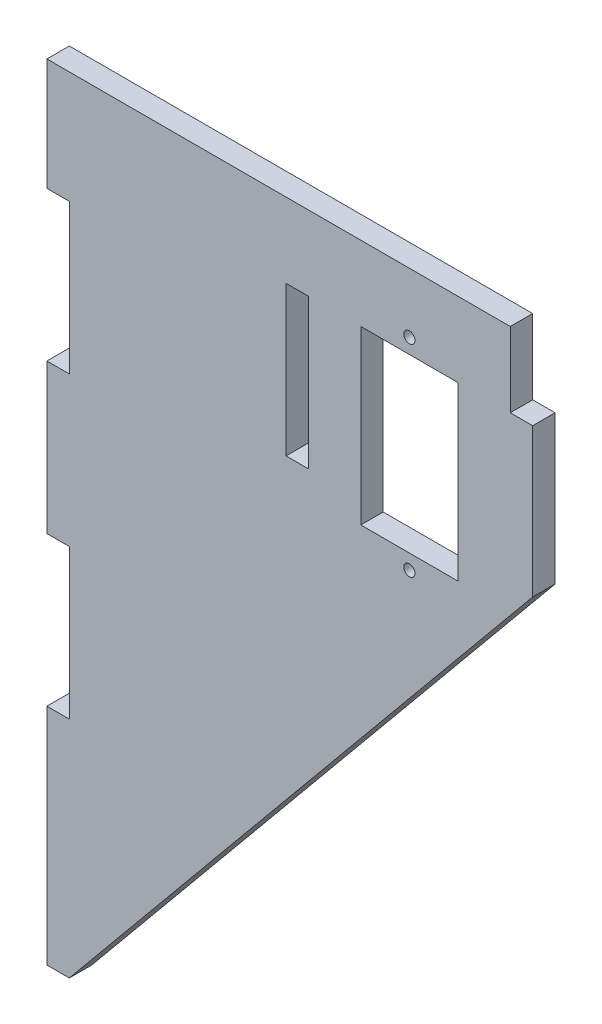
SolidWorks part; units mm, degrees
material "Acrilico TEC"
ref_plane "Front Plane" through (0, 0, 0) normal (0, 0, 1) x (1, 0, 0)
ref_plane "Top Plane" through (0, 0, 0) normal (0, 1, 0) x (1, 0, 0)
ref_plane "Right Plane" through (0, 0, 0) normal (1, 0, 0) x (0, 0, -1)
sketch "Sketch1" plane through (0, 0, 0) normal (0, 0, 1) x (1, 0, 0)
  line L0 (-3, 70) -> (-3, 50)
  line L1 (-3, 50) -> (0, 50)
  line L2 (0, 50) -> (0, 30)
  line L3 (0, 30) -> (-3, 30)
  line L4 (-3, 30) -> (-3, 0)
  line L5 (-3, 70) -> (0, 70)
  line L6 (0, 70) -> (0, 90)
  line L7 (0, 90) -> (-3, 90)
  line L8 (-3, 90) -> (-3, 105)
  line L9 (-3, 105) -> (15, 105)
  line L10 (15, 105) -> (15, 90) construction
  line L11 (-3, 0) -> (0, 0)
  line L12 (15, 105) -> (59, 105)
  line L13 (39, 72) -> (52, 72)
  line L14 (29, 95) -> (32, 95)
  line L15 (29, 75) -> (29, 95)
  line L16 (32, 75) -> (29, 75)
  line L17 (59, 105) -> (59, 95)
  line L18 (59, 95) -> (62, 95)
  line L19 (62, 95) -> (62, 75.1515)
  line L20 (52, 95) -> (52, 72)
  line L21 (39, 72) -> (39, 95)
  line L22 (0, 0) -> (62, 75.1515)
  line L23 (0, 0) -> (26.7162, 0) construction
  line L24 (39, 95) -> (52, 95)
  line L25 (32, 75) -> (32, 95)
  line L26 (52, 83.5) -> (39, 83.5) construction
  line L27 (45.5, 95) -> (45.5, 97) construction
  circle A0 centre (45.5, 97) radius 0.75
  circle A1 centre (45.5, 70) radius 0.75
  dimension "D23" = 1.5
  dimension "D1" = 15
  dimension "D2" = 20
  dimension "D3" = 20
  dimension "D4" = 20
  dimension "D5" = 30
  dimension "D6" = 3
  dimension "D7" = 3
  dimension "D8" = 15
  dimension "D9" = 15
  dimension "D10" = 44
  dimension "D11" = 3
  dimension "D12" = 10
  dimension "D13" = 7
  dimension "D14" = 20
  dimension "D15" = 3
  dimension "D16" = 3
  dimension "D17" = 14
  dimension "D18" = 10
  dimension "D19" = 50.477
  dimension "D20" = 23
  dimension "D21" = 19.8485
  dimension "D22" = 2
extrude "Boss-Extrude1" add sketch "Sketch1" along normal blind 3
